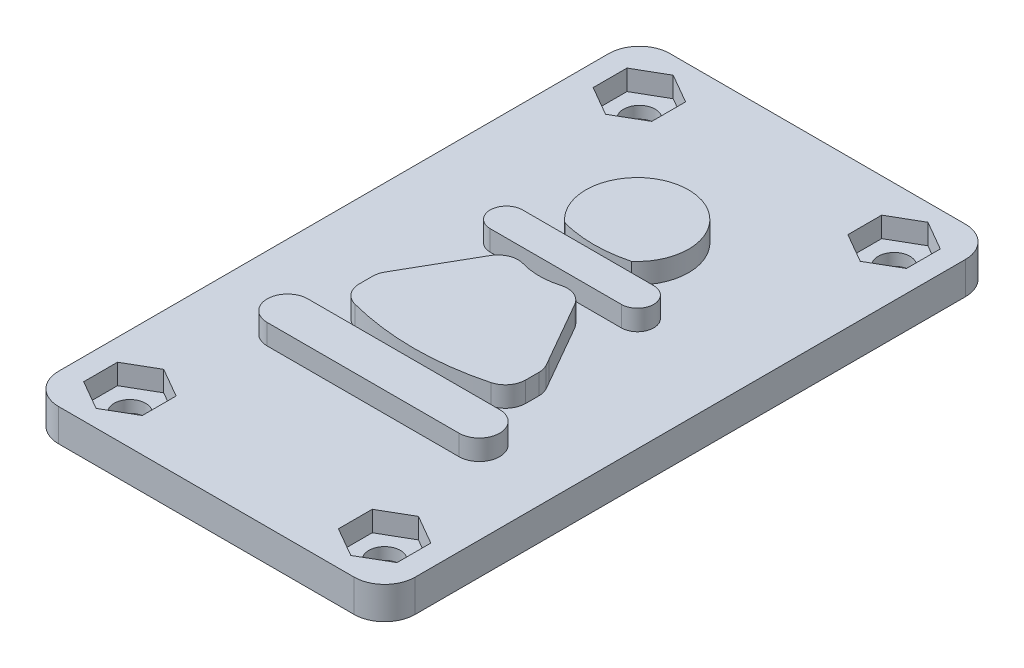
SolidWorks part; units mm, degrees
ref_plane "Front Plane" through (0, 0, 0) normal (0, 0, 1) x (1, 0, 0)
ref_plane "Top Plane" through (0, 0, 0) normal (0, 1, 0) x (1, 0, 0)
ref_plane "Right Plane" through (0, 0, 0) normal (1, 0, 0) x (0, 0, -1)
sketch "Sketch1" plane through (0, 0, 0) normal (0, 1, 0) x (1, 0, 0)
  line L1 (-12.5, -25) -> (12.5, -25) construction
  line L2 (-12.5, -25) -> (-12.5, 25) construction
  line L3 (-12.5, 25) -> (12.5, 25) construction
  line L4 (12.5, -25) -> (12.5, 25) construction
  line L5 (-12.5, -25) -> (12.5, 25) construction
  line L6 (-12.5, 25) -> (12.5, -25) construction
  line L7 (-17.5, -30) -> (17.5, -30)
  line L8 (-17.5, -30) -> (-17.5, 30)
  line L9 (-17.5, 30) -> (17.5, 30)
  line L10 (17.5, -30) -> (17.5, 30)
  line L11 (-17.5, -30) -> (17.5, 30) construction
  line L12 (-17.5, 30) -> (17.5, -30) construction
  line L13 (-12.5, 28.3198) -> (-15.375, 26.6599)
  line L14 (-15.375, 26.6599) -> (-15.375, 23.3401)
  line L15 (-15.375, 23.3401) -> (-12.5, 21.6802)
  line L16 (-12.5, 21.6802) -> (-9.625, 23.3401)
  line L17 (-9.625, 23.3401) -> (-9.625, 26.6599)
  line L18 (-9.625, 26.6599) -> (-12.5, 28.3198)
  line L19 (12.5, 28.3198) -> (9.625, 26.6599)
  line L20 (9.625, 26.6599) -> (9.625, 23.3401)
  line L21 (9.625, 23.3401) -> (12.5, 21.6802)
  line L22 (12.5, 21.6802) -> (15.375, 23.3401)
  line L23 (15.375, 23.3401) -> (15.375, 26.6599)
  line L24 (15.375, 26.6599) -> (12.5, 28.3198)
  line L25 (-12.5, -28.3198) -> (-9.625, -26.6599)
  line L26 (-9.625, -26.6599) -> (-9.625, -23.3401)
  line L27 (-9.625, -23.3401) -> (-12.5, -21.6802)
  line L28 (-12.5, -21.6802) -> (-15.375, -23.3401)
  line L29 (-15.375, -23.3401) -> (-15.375, -26.6599)
  line L30 (-15.375, -26.6599) -> (-12.5, -28.3198)
  line L31 (12.5, -21.6802) -> (9.625, -23.3401)
  line L32 (9.625, -23.3401) -> (9.625, -26.6599)
  line L33 (9.625, -26.6599) -> (12.5, -28.3198)
  line L34 (12.5, -28.3198) -> (15.375, -26.6599)
  line L35 (15.375, -26.6599) -> (15.375, -23.3401)
  line L36 (15.375, -23.3401) -> (12.5, -21.6802)
  circle A0 centre (-12.5, 25) radius 1.55
  circle A1 centre (12.5, 25) radius 1.55
  circle A2 centre (-12.5, -25) radius 1.55
  circle A3 centre (12.5, -25) radius 1.55
  circle A4 centre (-12.5, 25) radius 2.875 construction
  circle A5 centre (12.5, 25) radius 2.875 construction
  circle A6 centre (-12.5, -25) radius 2.875 construction
  circle A7 centre (12.5, -25) radius 2.875 construction
  point P0 (0, 0)
  point P10 (0, 0)
  dimension "D3" = 3.1
  dimension "D6" = 5.75
  dimension "D1" = 50
  dimension "D2" = 25
  dimension "D4" = 60
  dimension "D5" = 35
extrude "Boss-Extrude1" add sketch "Sketch1" along normal blind 3.175 contours L7 L10 L9 L8 L36 L35 L34 L33 L32 L31 L30 L29 L28 L27 L26 L25 L24 L23 L22 L21 L20 L19 L18 L17 L16 L15 L14 L13 | L17 L18 L13 L14 L15 L16 A0 | L23 L24 L19 L20 L21 L22 A1 | L35 L36 L31 L32 L33 L34 A3 | L29 L30 L25 L26 L27 L28 A2 region at (0, 0, 0) region at (-11.1064, 0, -27.4138) region at (13.8936, 0, -27.4138) region at (-13.8936, 0, 27.4138) region at (13.8936, 0, 22.5862)
extrude "Cut-Extrude1" cut sketch "Sketch1<3>" against normal blind 2 from surface contours L29 L30 L25 L26 L27 L28 A2 | L17 L18 L13 L14 L15 L16 A0 | L23 L24 L19 L20 L21 L22 A1 | L35 L36 L31 L32 L33 L34 A3 region at (-11.1064, 0, -27.4138) region at (13.8936, 0, -27.4138) region at (-13.8936, 0, 27.4138) region at (13.8936, 0, 22.5862) starting at face at (0, 3.175, 0)
sketch "Sketch1<3>" plane through (0, 0, 0) normal (0, 1, 0) x (1, 0, 0) same geometry as "Sketch1"
sketch "Sketch2" plane through (0, 3.175, 0) normal (0, 1, 0) x (1, 0, 0)
  line L3 (-3.2694, 3.5464) -> (-7.535, -3.8944)
  line L4 (7.535, -3.8944) -> (3.2694, 3.5464)
  line L5 (-3.2694, 3.5464) -> (3.2694, 3.5464) construction
  line L6 (-6.4344, 5.8874) -> (6.4344, 5.8874) construction
  line L7 (-6.4344, 7.4785) -> (6.4344, 7.4785)
  line L8 (-6.4344, 4.2964) -> (6.4344, 4.2964)
  line L9 (-8.1654, -5.0149) -> (-8.1654, -8.3102)
  line L10 (8.1654, -5.0149) -> (8.1654, -8.3102)
  line L11 (0, 3.5464) -> (0, -9.6177) construction
  line L12 (-9.4119, -12.6177) -> (9.4119, -12.6177) construction
  line L13 (-9.4119, -10.6177) -> (9.4119, -10.6177)
  line L14 (-9.4119, -14.6177) -> (9.4119, -14.6177)
  arc A0 (-3.2694, 8.4485) -> (3.2694, 8.4485) centre (0, 12.2891) cw
  arc A1 (-3.2694, 8.4485) -> (3.2694, 8.4485) centre (0, 20.8684) ccw
  arc A3 (-7.535, -3.8944) -> (-8.1654, -5.0149) centre (62.0717, -43.7978) ccw
  arc A5 (8.1654, -5.0149) -> (7.535, -3.8944) centre (-62.0717, -43.7978) ccw
  arc A6 (3.2694, 3.5464) -> (-3.2694, 3.5464) centre (0, 9.2494) cw
  arc A7 (-6.4344, 7.4785) -> (-6.4344, 4.2964) centre (-6.4344, 5.8874) ccw
  arc A8 (6.4344, 4.2964) -> (6.4344, 7.4785) centre (6.4344, 5.8874) ccw
  arc A9 (-8.1654, -8.3102) -> (8.1654, -8.3102) centre (0, 16.5321) ccw
  arc A10 (-9.4119, -10.6177) -> (-9.4119, -14.6177) centre (-9.4119, -12.6177) ccw
  arc A11 (9.4119, -14.6177) -> (9.4119, -10.6177) centre (9.4119, -12.6177) ccw
  point P7 (0, 5.8874)
  point P19 (0, 3.5464)
  point P25 (0, -12.6177)
  dimension "D1" = 0.75
  dimension "D2" = 1
  dimension "D3" = 4
extrude "Boss-Extrude2" add sketch "Sketch2" along normal blind 2
fillet "Fillet1" radius 2 6 edges at (8.1654, 4.175, 8.3102) (-8.1654, 4.175, 8.3102) (-8.1654, 4.175, 5.0149) (8.1654, 4.175, 5.0149) (3.2694, 4.175, -3.5464) (-3.2694, 4.175, -3.5464)
fillet "Fillet2" radius 3 4 edges at (-17.5, 1.5875, -30) (17.5, 1.5875, -30) (17.5, 1.5875, 30) (-17.5, 1.5875, 30)
